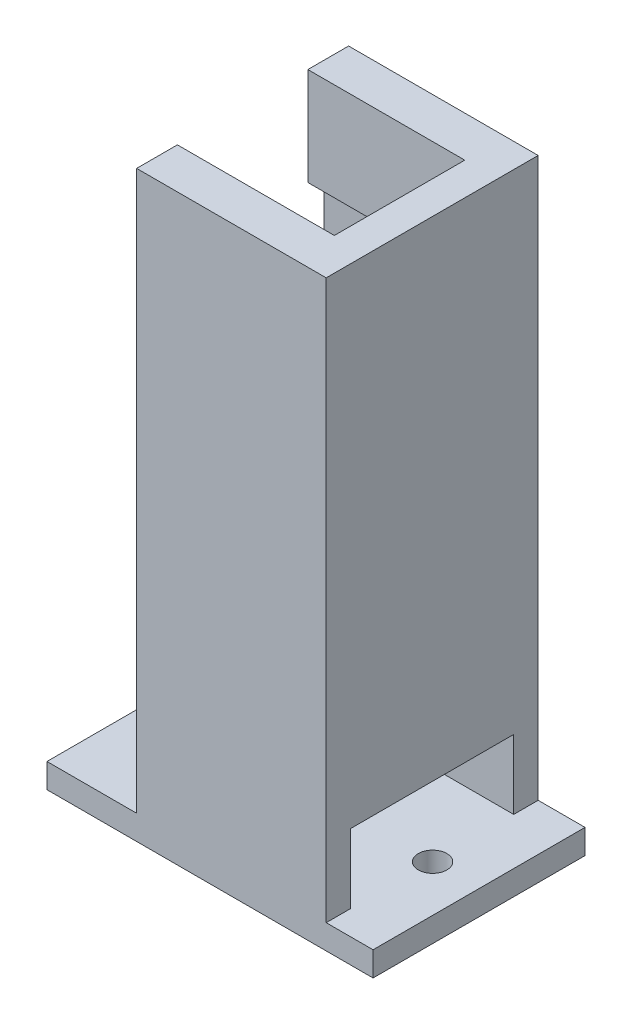
SolidWorks part; units mm, degrees
ref_plane "Front Plane" through (0, 0, 0) normal (0, 0, 1) x (1, 0, 0)
ref_plane "Top Plane" through (0, 0, 0) normal (0, 1, 0) x (1, 0, 0)
ref_plane "Right Plane" through (0, 0, 0) normal (1, 0, 0) x (0, 0, -1)
sketch "Sketch1" plane through (0, 0, 0) normal (0, 1, 0) x (1, 0, 0)
  line L1 (-20, 13) -> (20, 13)
  line L2 (-20, 13) -> (-20, -13)
  line L3 (-20, -13) -> (20, -13)
  line L4 (20, 13) -> (20, -13)
  dimension "D1" = 40
  dimension "D2" = 26
  dimension "D3" = 13
  dimension "D4" = 20
extrude "Boss-Extrude1" add sketch "Sketch1" along normal blind 3 contours L1 L4 L3 L2
sketch "Sketch2" plane through (0, 3, 0) normal (0, 1, 0) x (1, 0, 0)
  line L0 (20, 0) -> (14.3, 0) construction
  line L1 (20, 13) -> (20, -13) construction
  line L2 (0, 13) -> (0, -13) construction
  line L3 (-20, 13) -> (20, 13) construction
  line L4 (-20, -13) -> (20, -13) construction
  line L5 (-20, 0) -> (-14.3, 0) construction
  circle A0 centre (14.3, 0) radius 1.75
  circle A1 centre (-14.3, 0) radius 1.75
extrude "Cut-Extrude1" cut sketch "Sketch2" against normal blind 3
sketch "Sketch3" plane through (0, 3, 0) normal (0, 1, 0) x (1, 0, 0)
  line L0 (-20, 13) -> (20, 13) construction
  line L1 (0, 0) -> (50000, 0) construction
  line L2 (0, 0) -> (0, 50000) construction
  line L3 (-9, -10) -> (10.25, -10)
  line L4 (-9, 13) -> (10.25, 13)
  line L5 (-9, 13) -> (-9, 10)
  line L6 (-9, 10) -> (10.25, 10)
  line L7 (10.25, 13) -> (10.25, 10)
  line L8 (10.25, -13) -> (10.25, -10)
  line L9 (-9, -13) -> (10.25, -13)
  line L10 (-9, -13) -> (-9, -10)
  line L11 (0, 0) -> (10.5, 0) construction
  point P0 (-9, 13)
  point P9 (9, 13)
  dimension "D1" = 11
  dimension "D2" = 3
  dimension "D3" = 19.25
extrude "Boss-Extrude2" add sketch "Sketch3" along normal blind 56.5
sketch "Sketch5" plane through (0, 59.5, 0) normal (0, 1, 0) x (1, 0, 0)
  line L0 (-9, 13) -> (-9, -13) construction
  line L1 (-9, -8) -> (-9, 8) construction
  line L2 (-9, 0) -> (49991, 0) construction
  line L3 (-9, 13) -> (10.25, 13)
  line L4 (-9, 13) -> (-9, 8)
  line L5 (-9, 8) -> (10.25, 8)
  line L6 (10.25, 13) -> (10.25, 8)
  line L11 (-9, -8) -> (10.25, -8)
  line L12 (10.25, -13) -> (10.25, -8)
  line L13 (-9, -13) -> (10.25, -13)
  line L14 (-9, -13) -> (-9, -8)
  point P7 (-9, 0)
  dimension "D1" = 26
  dimension "D2" = 19.25
extrude "Boss-Extrude4" add sketch "Sketch5" along normal blind 12
sketch "Sketch6" plane through (0, 3, 0) normal (0, 1, 0) x (1, 0, 0)
  circle A0 centre (0, 0) radius 2.5
extrude "Cut-Extrude2" cut sketch "Sketch6" against normal blind 15
sketch "Sketch7" plane through (10.25, 0, 0) normal (1, 0, 0) x (0, 0, -1)
  line L0 (13, 3) -> (-13, 3) construction
  line L1 (-13, 71.5) -> (-13, 3) construction
  line L3 (-13, 3) -> (13, 3)
  line L4 (-13, 3) -> (-13, 71.5)
  line L5 (-13, 71.5) -> (13, 71.5)
  line L6 (13, 3) -> (13, 71.5)
extrude "Boss-Extrude5" add sketch "Sketch7" along normal blind 4
sketch "Sketch9" plane through (14.25, 0, 0) normal (1, 0, 0) x (0, 0, -1)
  line L0 (-13, 3) -> (-10, 3) construction
  line L1 (-13, 3) -> (-1.7493, 3) construction
  line L2 (13, 3) -> (10, 3) construction
  line L3 (13, 3) -> (-13, 3) construction
  line L4 (-10, 3) -> (-10, 11.5) construction
  line L6 (-10, 3) -> (10, 3)
  line L7 (-10, 3) -> (-10, 11.5)
  line L8 (-10, 11.5) -> (10, 11.5)
  line L9 (10, 3) -> (10, 11.5)
extrude "Cut-Extrude3" cut sketch "Sketch9" against normal blind 4
